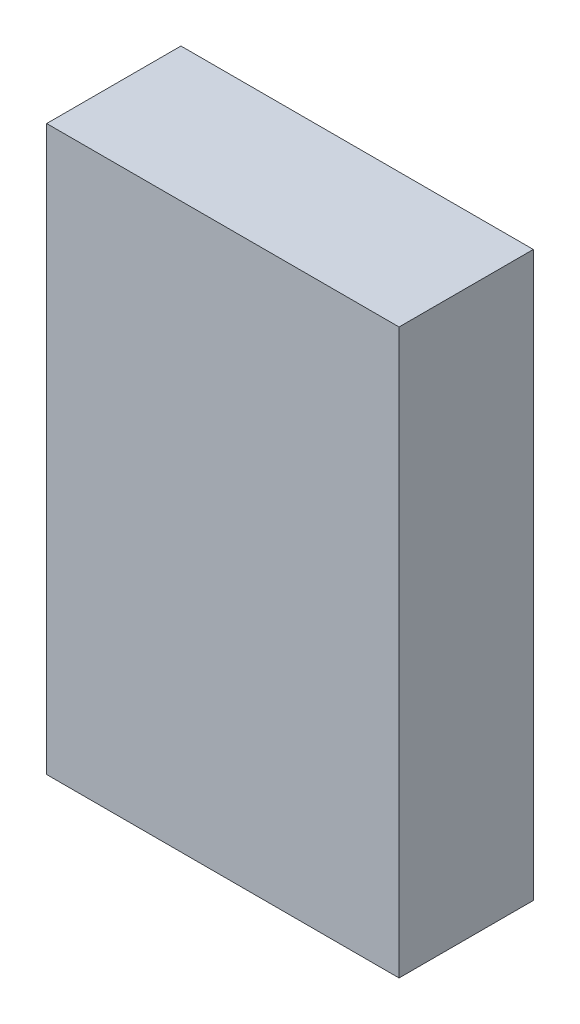
SolidWorks part; units mm, degrees
material "POLYURETHANE (11671)"
ref_plane "Front Plane" through (0, 0, 0) normal (0, 0, 1) x (1, 0, 0)
ref_plane "Top Plane" through (0, 0, 0) normal (0, 1, 0) x (1, 0, 0)
ref_plane "Right Plane" through (0, 0, 0) normal (1, 0, 0) x (0, 0, -1)
sketch "Sketch1" plane through (0, 0, 0) normal (0, 0, 1) x (1, 0, 0)
  line L1 (-12.5, 20) -> (12.5, 20)
  line L2 (-12.5, 20) -> (-12.5, -20)
  line L3 (-12.5, -20) -> (12.5, -20)
  line L4 (12.5, 20) -> (12.5, -20)
  line L5 (-12.5, 20) -> (12.5, -20) construction
  line L6 (-12.5, -20) -> (12.5, 20) construction
  point P0 (0, 0)
  dimension "D1" = 25
  dimension "D2" = 40
extrude "Boss-Extrude1" add sketch "Sketch1" along normal blind 9.525
